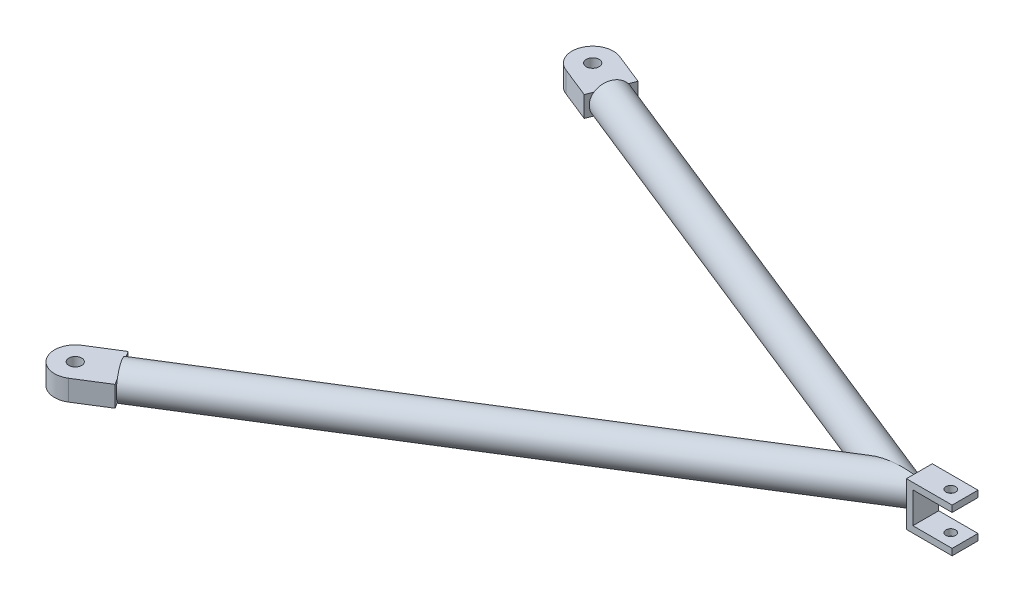
SolidWorks part; units mm, degrees
ref_plane "Front Plane" through (0, 0, 0) normal (0, 0, 1) x (1, 0, 0)
ref_plane "Top Plane" through (0, 0, 0) normal (0, 1, 0) x (1, 0, 0)
ref_plane "Right Plane" through (0, 0, 0) normal (1, 0, 0) x (0, 0, -1)
sketch "Sketch1" plane through (0, 0, 0) normal (0, 1, 0) x (1, 0, 0)
  line L0 (0, 0) -> (-247.6207, 99.06)
  line L1 (0, 0) -> (-247.6207, -154.94)
  line L2 (-247.6207, 99.06) -> (-247.6207, -154.94) construction
  dimension "D1" = 266.7
  dimension "D2" = 292.1
  dimension "D3" = 254
ref_plane "Plane1" through (-247.6207, 0, 154.94) normal (-0.8477, 0, 0.5304) x (0.5304, 0, 0.8477)
sketch "Sketch2" plane through (-247.6207, 0, 154.94) normal (-0.8477, 0, 0.5304) x (0.5304, 0, 0.8477)
  circle A0 centre (0, 0) radius 8.255
  dimension "D1" = 16.51
sweep "Sweep1" add profiles "Sketch2" path "Sketch1"
sketch "Sketch3" plane through (0, 0, 0) normal (0, 0, 1) x (1, 0, 0)
  line L0 (34.2567, -10.795) -> (11.811, -10.795)
  line L1 (11.811, -10.795) -> (11.811, 10.795)
  line L2 (11.811, 10.795) -> (34.2567, 10.795)
  line L3 (34.2567, 10.795) -> (34.2567, 7.62)
  line L4 (34.2567, 7.62) -> (14.986, 7.62)
  line L5 (14.986, 7.62) -> (14.986, -7.62)
  line L6 (14.986, -7.62) -> (34.2567, -7.62)
  line L7 (34.2567, -7.62) -> (34.2567, -10.795)
  line L8 (-18.161, 0) -> (18.161, 0) construction
  ellipse E0 centre (0, 0) end of major axis (18.161, 0) minor radius 8.255 construction
  ellipse E1 centre (0, 0) end of major axis (18.161, 0) minor radius 8.255 construction
  point P21 (11.811, 0)
  dimension "D1" = 3.175
  dimension "D2" = 15.24
  dimension "D3" = 3.175
  dimension "D4" = 6.35
extrude "Boss-Extrude1" add sketch "Sketch3" along normal blind 6.35 and the other way blind 6.35
sketch "Sketch4" plane through (-247.6207, 0, 154.94) normal (-0.8477, 0, 0.5304) x (0.5304, 0, 0.8477)
  line L1 (-10.16, 5.08) -> (10.16, 5.08)
  line L2 (-10.16, 5.08) -> (-10.16, -5.08)
  line L3 (-10.16, -5.08) -> (10.16, -5.08)
  line L4 (10.16, 5.08) -> (10.16, -5.08)
  line L5 (-10.16, 5.08) -> (10.16, -5.08) construction
  line L6 (-10.16, -5.08) -> (10.16, 5.08) construction
  point P0 (0, 0)
  dimension "D1" = 20.32
  dimension "D2" = 10.16
extrude "Boss-Extrude2" add sketch "Sketch4" along normal blind 10.16 and the other way blind 16.51
sketch "Sketch5" plane through (-247.6207, 0, -99.06) normal (-0.9285, 0, -0.3714) x (-0.3714, 0, 0.9285)
  line L1 (-10.16, 5.08) -> (10.16, 5.08)
  line L2 (-10.16, 5.08) -> (-10.16, -5.08)
  line L3 (-10.16, -5.08) -> (10.16, -5.08)
  line L4 (10.16, 5.08) -> (10.16, -5.08)
  line L5 (-10.16, 5.08) -> (10.16, -5.08) construction
  line L6 (-10.16, -5.08) -> (10.16, 5.08) construction
  point P0 (0, 0)
  dimension "D1" = 20.32
  dimension "D2" = 10.16
extrude "Boss-Extrude3" add sketch "Sketch5" along normal blind 10.16 and the other way blind 16.256
sketch "Sketch7" plane through (0, 5.08, 0) normal (0, 1, 0) x (1, 0, 0)
  line L8 (-236.3013, 83.5889) -> (-234.9444, 86.9807)
  line L9 (-234.9444, 86.9807) -> (-250.0375, 93.0187)
  line L10 (-250.0375, 93.0187) -> (-245.2039, 105.1013)
  line L11 (-245.2039, 105.1013) -> (-230.1108, 99.0634)
  line L12 (-230.1108, 99.0634) -> (-228.7539, 102.4552)
  line L13 (-228.7539, 102.4552) -> (-253.2801, 112.2669)
  line L14 (-253.2801, 112.2669) -> (-260.8276, 93.4005)
  line L15 (-260.8276, 93.4005) -> (-236.3013, 83.5889)
  line L22 (-257.0539, 102.8337) -> (-260.8276, 93.4005)
  line L23 (-260.8276, 93.4005) -> (-251.3944, 89.6268)
  arc A0 (-257.0539, 102.8337) -> (-251.3944, 89.6268) centre (-247.6207, 99.06) ccw
  dimension "D1" = 0
extrude "Cut-Extrude1" cut sketch "Sketch7" against normal through all
ref_plane "Plane2" through (0, 0, 0) normal (-0.3714, 0, 0.9285) x (0.9285, 0, 0.3714)
mirror "Mirror1" about plane through (0, 0, 0) normal (-0.3714, 0, 0.9285) of "Cut-Extrude1"
sketch "Sketch9" plane through (0, 5.08, 0) normal (0, 1, 0) x (1, 0, 0)
  line L0 (-239.014, -137.5696) -> (-261.6228, -151.7163) construction
  line L1 (-228.2355, -154.7954) -> (-250.8444, -168.9421) construction
  line L2 (-250.8444, -168.9421) -> (-261.6228, -151.7163) construction
  line L3 (-242.2315, -163.5529) -> (-250.8444, -168.9421)
  line L4 (-250.8444, -168.9421) -> (-256.2336, -160.3292)
  arc A0 (-256.2336, -160.3292) -> (-242.2315, -163.5529) centre (-247.6207, -154.94) ccw
extrude "Cut-Extrude2" cut sketch "Sketch9" against normal through all
ref_plane "Plane3" through (0, 0, 0) normal (0.5304, 0, 0.8477) x (0.8477, 0, -0.5304)
mirror "Mirror2" about plane through (0, 0, 0) normal (0.5304, 0, 0.8477) of "Cut-Extrude2"
sketch "Sketch10" plane through (-247.6207, 0, 154.94) normal (-0.8477, 0, 0.5304) x (0.5304, 0, 0.8477)
  line L0 (6.5068, -5.08) -> (-6.5068, -5.08) construction
  line L1 (-6.5068, 5.08) -> (6.5068, 5.08) construction
  line L2 (6.5068, -5.08) -> (-6.5068, -5.08)
  line L3 (-6.5068, 5.08) -> (6.5068, 5.08)
  arc A0 (-6.5068, -5.08) -> (6.5068, -5.08) centre (0, 0) ccw construction
  arc A1 (6.5068, 5.08) -> (-6.5068, 5.08) centre (0, 0) ccw construction
  arc A2 (-6.5068, -5.08) -> (6.5068, -5.08) centre (0, 0) ccw
  arc A3 (6.5068, 5.08) -> (-6.5068, 5.08) centre (0, 0) ccw
extrude "Cut-Extrude3" cut sketch "Sketch10" against normal up to surface (16.51 mm away) up to face at (-228.9726, 0, 153.6175)
sketch "Sketch11" plane through (-247.6207, 0, -99.06) normal (-0.9285, 0, -0.3714) x (-0.3714, 0, 0.9285)
  line L0 (6.5068, -5.08) -> (-6.5068, -5.08) construction
  line L1 (-6.5068, 5.08) -> (6.5068, 5.08) construction
  line L2 (6.5068, -5.08) -> (-6.5068, -5.08)
  line L3 (-6.5068, 5.08) -> (6.5068, 5.08)
  arc A0 (-6.5068, -5.08) -> (6.5068, -5.08) centre (0, 0) ccw construction
  arc A1 (6.5068, 5.08) -> (-6.5068, 5.08) centre (0, 0) ccw construction
  arc A2 (-6.5068, -5.08) -> (6.5068, -5.08) centre (0, 0) ccw
  arc A3 (6.5068, 5.08) -> (-6.5068, 5.08) centre (0, 0) ccw
extrude "Cut-Extrude4" cut sketch "Sketch11" along direction (0.9285, 0, 0.3714) on the side against the normal up to surface (16.256 mm away) up to face at (-235.7852, 0, -84.879)
sketch "Sketch12" plane through (0, 0, 6.35) normal (0, 0, 1) x (1, 0, 0)
  line L1 (14.986, 4.6631) -> (14.986, -4.6631)
  line L2 (14.986, 4.6631) -> (14.986, -4.6631)
  ellipse E1 centre (0, 0) end of major axis (18.161, 0) minor radius 8.255 (14.986, -4.6631) -> (14.986, 4.6631) ccw
  ellipse E2 centre (0, 0) end of major axis (18.161, 0) minor radius 8.255 (14.986, -4.6631) -> (14.986, 4.6631) ccw
  dimension "D1" = 0
extrude "Cut-Extrude5" cut sketch "Sketch12" against normal through all
sketch "Sketch13" plane through (0, 5.08, 0) normal (0, 1, 0) x (1, 0, 0)
  point P0 (-247.6207, 99.06)
  point P1 (-247.6207, -154.94)
  point P3 (0, 0)
hole_wizard "E (0.25) Diameter Hole1" positions "3DSketch1" profile "Sketch14" hole size "E" standard "ANSI Inch"
sketch3d "3DSketch1"
  point P0 (-247.6207, 5.08, -99.06)
  point P3 (-247.6207, 5.08, 154.94)
sketch "Sketch14" plane through (-247.6207, 5.08, -99.06) normal (1, 0, 0) x (0, 0, 1)
  line L0 (0, 0) -> (0, 20.9577)
  line L1 (0, 20.9577) -> (3.175, 19.05)
  line L2 (3.175, 19.05) -> (3.175, 0)
  line L5 (3.175, 0) -> (0, 0)
  line L10 (0, 20.9577) -> (-3.175, 19.05) construction
  line L11 (0, -6.35) -> (0, 107.95) construction
  dimension "Hole Dia." = 6.35
  dimension "Hole Depth" = 19.05
  dimension "Drill Angle" = 118
hole_wizard "3/16 (0.1875) Diameter Hole1" positions "Sketch15" profile "Sketch16" hole size "3/16" standard "ANSI Inch" end condition through all
sketch "Sketch15" plane through (0, 10.795, 0) normal (0, 1, 0) x (1, 0, 0)
  line L0 (-11.8745, 0) -> (11.8745, 0) construction
  point P0 (27.2415, 0)
sketch "Sketch16" plane through (27.2415, 10.795, 0) normal (1, 0, 0) x (0, 0, 1)
  line L0 (0, 0) -> (0, 21.59)
  line L1 (0, 21.59) -> (2.3812, 21.59)
  line L2 (2.3812, 21.59) -> (2.3812, 0)
  line L5 (2.3812, 0) -> (0, 0)
  line L11 (0, -6.35) -> (0, 107.95) construction
  dimension "Thru Hole Dia." = 4.7625
  dimension "Thru Hole Depth" = 21.59
ref_point "Point1"
ref_point "Point2"
sketch3d "3DSketch2"
  line L0 (27.2415, 7.62, 0) -> (27.2415, -7.62, 0) construction
  circle A0 centre (27.2415, 7.62, 0) radius 2.3812 construction
  circle A1 centre (27.2415, -7.62, 0) radius 2.3812 construction
  circle A2 centre (27.2415, 7.62, 0) radius 2.3812 construction
  circle A3 centre (27.2415, -7.62, 0) radius 2.3812 construction
  point P2 (27.2415, 5.2388, 0)
  point P5 (27.2415, -5.2388, 0)
  point P7 (27.2415, 5.2388, 0)
  point P9 (27.2415, -5.2388, 0)
  point P10 (27.2415, 0, 0)
ref_point "JOINT"
